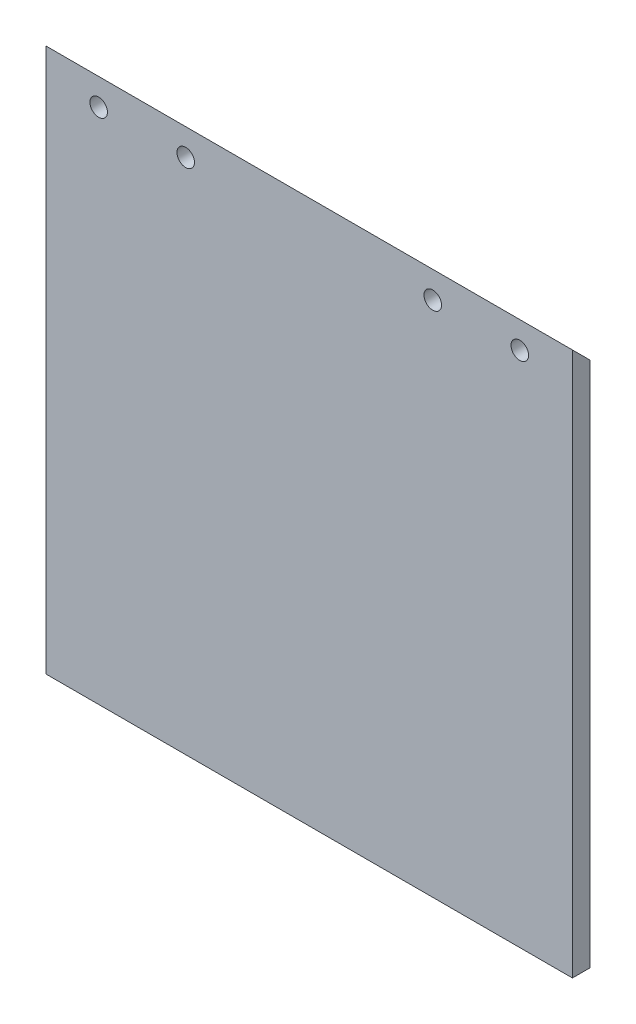
SolidWorks part; units mm, degrees
ref_plane "Front Plane" through (0, 0, 0) normal (0, 0, 1) x (1, 0, 0)
ref_plane "Top Plane" through (0, 0, 0) normal (0, 1, 0) x (1, 0, 0)
ref_plane "Right Plane" through (0, 0, 0) normal (1, 0, 0) x (0, 0, -1)
sketch "Sketch1" plane through (0, 0, 0) normal (0, 0, 1) x (1, 0, 0)
  line L1 (0, 0) -> (-95.25, 0)
  line L2 (0, 0) -> (0, 98.425)
  line L3 (0, 98.425) -> (-95.25, 98.425)
  line L4 (-95.25, 0) -> (-95.25, 98.425)
  dimension "D1" = 95.25
  dimension "D2" = 98.425
extrude "Boss-Extrude1" add sketch "Sketch1" along normal blind 3.175 contours L4 L3 L2 L1
chamfer "Chamfer1" distance 3.175 angle 45 1 edges at (-47.625, 98.425, 0)
sketch "Sketch2" plane through (0, 0, 3.175) normal (0, 0, 1) x (1, 0, 0)
  line L0 (-95.25, 0) -> (-95.25, 98.425) construction
  line L1 (0, 0) -> (0, 98.425) construction
  line L2 (0, 98.425) -> (-95.25, 98.425) construction
  circle A0 centre (-85.725, 93.599) radius 1.5875
  circle A1 centre (-69.977, 93.599) radius 1.5875
  circle A2 centre (-25.273, 93.599) radius 1.5875
  circle A3 centre (-9.525, 93.599) radius 1.5875
  dimension "D6" = 3.175
  dimension "D1" = 9.525
  dimension "D2" = 9.525
  dimension "D3" = 15.748
  dimension "D4" = 15.748
  dimension "D5" = 4.826
extrude "Cut-Extrude1" cut sketch "Sketch2" against normal blind 17.78
